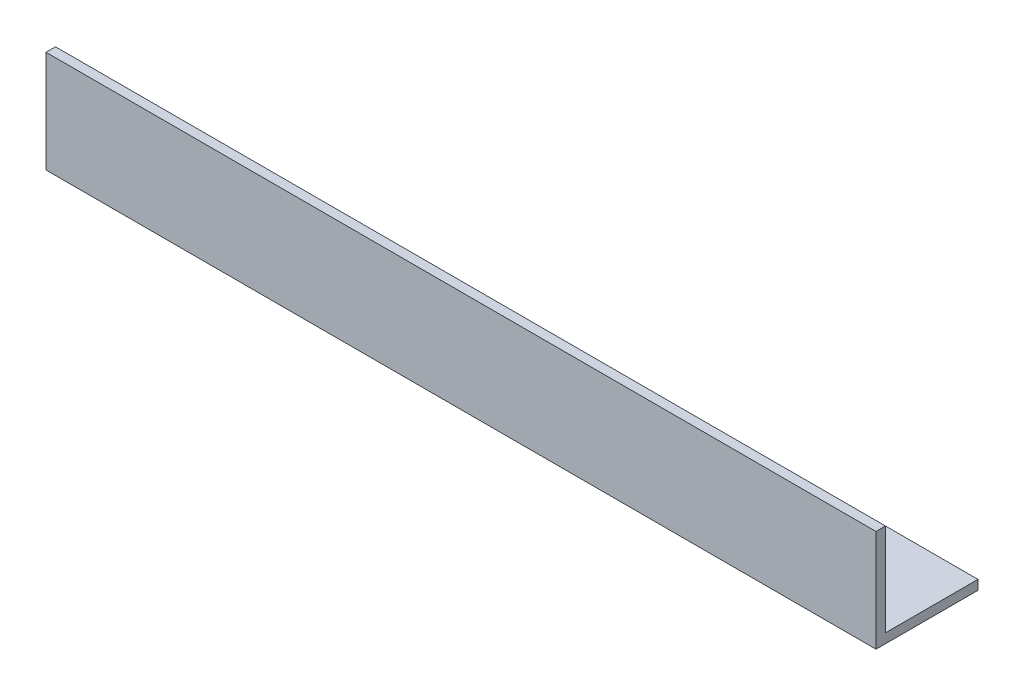
SolidWorks part; units mm, degrees
ref_plane "Спереди" through (0, 0, 0) normal (0, 0, 1) x (1, 0, 0)
ref_plane "Сверху" through (0, 0, 0) normal (0, 1, 0) x (1, 0, 0)
ref_plane "Справа" through (0, 0, 0) normal (1, 0, 0) x (0, 0, -1)
sketch "Эскиз1" plane through (0, 0, 0) normal (1, 0, 0) x (0, 0, -1)
  line L0 (0, 43) -> (0, 0)
  line L1 (0, 0) -> (43, 0)
extrude "Вытянуть-Тонкостенный1" add sketch "Эскиз1" along normal blind 350 thin thin type one direction reverse wall 4
